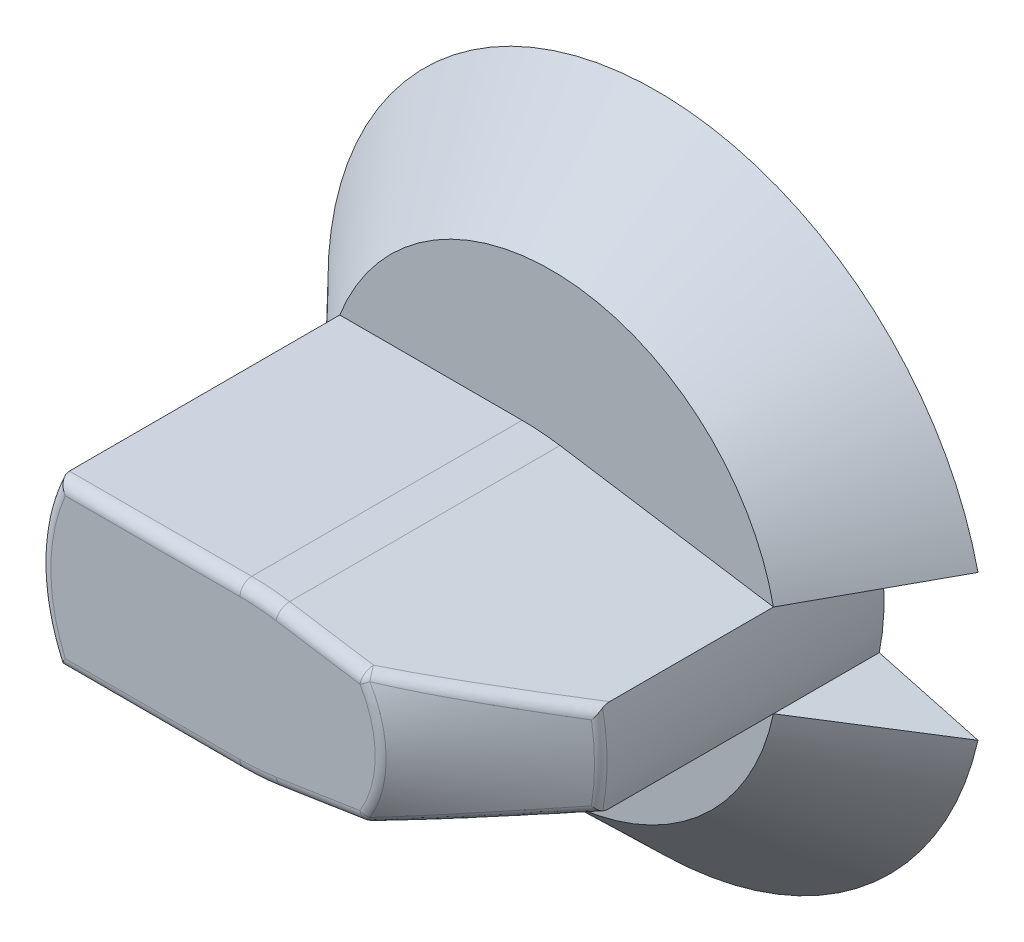
SolidWorks part; units mm, degrees
ref_plane "Płaszczyzna przednia" through (0, 0, 0) normal (0, 0, 1) x (1, 0, 0)
ref_plane "Płaszczyzna górna" through (0, 0, 0) normal (0, 1, 0) x (1, 0, 0)
ref_plane "Płaszczyzna prawa" through (0, 0, 0) normal (1, 0, 0) x (0, 0, -1)
sketch "Szkic1" plane through (0, 0, 0) normal (0, 0, 1) x (1, 0, 0)
  circle A0 centre (0, 0) radius 14
  circle A2 centre (0, 0) radius 9.15 construction
  dimension "D1" = 28
  dimension "D2" = 18.3
extrude "Dodanie-wyciągnięcie1" add sketch "Szkic1" along normal blind 4.5 contours A0
chamfer "Sfazowanie2" distance 4.5 angle 44 1 edges at (14, 0, 4.5)
sketch "Szkic2" plane through (0, 0, 4.5) normal (0, 0, 1) x (1, 0, 0)
  line L4 (9.4521, 1.9659) -> (-0.4295, 3.5)
  line L10 (8.9976, 3.5) -> (-8.9976, 3.5) construction
  line L11 (8.9976, 3.5) -> (8.9976, -3.5) construction
  line L12 (8.9976, -3.5) -> (-8.9976, -3.5) construction
  line L13 (-8.9976, 3.5) -> (-8.9976, -3.5) construction
  line L14 (8.9976, 3.5) -> (-8.9976, -3.5) construction
  line L15 (8.9976, -3.5) -> (-8.9976, 3.5) construction
  line L16 (-0.4295, 3.5) -> (-8.9976, 3.5)
  line L18 (-8.9976, -3.5) -> (-0.4295, -3.5)
  line L19 (-0.4295, -3.5) -> (9.4521, -1.9659)
  circle A0 centre (0, 0) radius 9.6544 construction
  arc A2 (9.4521, 1.9659) -> (9.4521, -1.9659) centre (0, 0) cw
  arc A3 (-8.9976, 3.5) -> (-8.9976, -3.5) centre (-1.6326, 0) ccw
  point P0 (0, 0)
  point P1 (0, 0)
  dimension "D2" = 1.6
  dimension "D3" = 1.6
  dimension "D6" = 8.1544
  dimension "D1" = 7
  dimension "D4" = 10
  dimension "D5" = 10
extrude "Dodanie-wyciągnięcie5" add sketch "Szkic2" along normal blind 12
sketch "Szkic8" plane through (0, 0, 0) normal (0, 0, -1) x (-1, 0, 0)
  line L0 (-9.4521, 1.9659) -> (-13.8613, 1.9659) construction
  line L1 (-9.4521, -1.9659) -> (-13.8613, -1.9659) construction
  line L2 (-9.4521, 1.9659) -> (-13.6543, 3.0919)
  line L3 (-9.4521, -1.9659) -> (-13.6543, -3.0919)
  arc A0 (-9.4521, 1.9659) -> (-9.4521, -1.9659) centre (0, 0) ccw construction
  arc A1 (-9.4521, 1.9659) -> (-9.4521, -1.9659) centre (0, 0) ccw
  circle A2 centre (0, 0) radius 14 construction
  arc A4 (-13.6543, -3.0919) -> (-13.6543, 3.0919) centre (-1.5427, 0) cw
  dimension "D1" = 15
  dimension "D2" = 15
extrude "Wytnij-wyciągnięcie2" cut sketch "Szkic8" against normal blind 8
chamfer "Sfazowanie4" distance 4.5 distance2 4.95 1 edges at (9.6544, 0, 16.5)
fillet "Zaokrąglenie2" radius 0.5 9 edges at (9.6544, 0, 12) (1.6557, 3.1763, 16.5) (1.6557, -3.1763, 16.5) (8.0162, 2.1888, 13.2225) (-9.787, 0, 16.5) (-4.7136, -3.5, 16.5) (-4.7136, 3.5, 16.5) (4.7044, 0, 16.5)
fillet "Zaokrąglenie3" radius 10.5 4 edges at (-0.4408, 3.3536, 16.3536) (-0.4408, -3.3536, 16.3536) (-0.4295, -3.5, 10.25) (-0.4295, 3.5, 10.25)
sketch "Szkic9" plane through (0, 0, 0) normal (0, 0, -1) x (-1, 0, 0)
  line L0 (1.17, -1.1492) -> (-1.17, -1.1492)
  arc A0 (1.17, -1.1492) -> (-1.17, -1.1492) centre (0, 0) ccw
  dimension "D1" = 3.28
  dimension "D2" = 2.34
extrude "Wytnij-wyciągnięcie3" cut sketch "Szkic9" against normal blind 6
